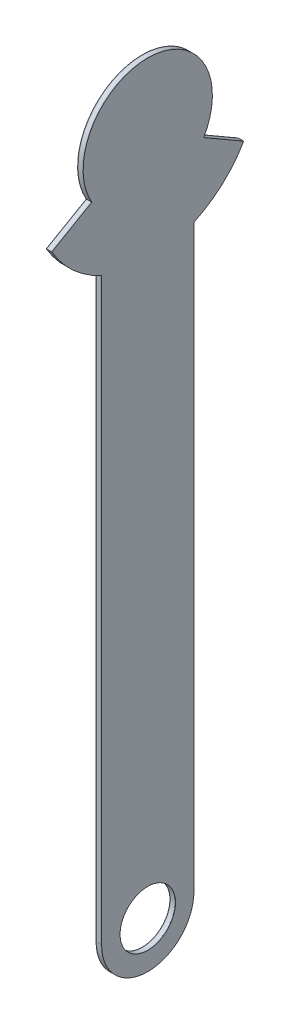
SolidWorks part; units mm, degrees
ref_plane "Front Plane" through (0, 0, 0) normal (0, 0, 1) x (1, 0, 0)
ref_plane "Top Plane" through (0, 0, 0) normal (0, 1, 0) x (1, 0, 0)
ref_plane "Right Plane" through (0, 0, 0) normal (1, 0, 0) x (0, 0, -1)
sketch "Sketch2" plane through (0, 0, 0) normal (1, 0, 0) x (0, 0, -1)
  line L0 (0, -196.8) -> (0, 196.8) construction
  line L2 (-30.3109, 179.3) -> (-51.9615, 166.8)
  line L3 (30.3109, 179.3) -> (51.9615, 166.8)
  line L9 (-25, 142.2564) -> (-25, -171.8)
  line L10 (25, 142.2564) -> (25, -171.8)
  circle A0 centre (0, 196.8) radius 35
  arc A1 (-51.9615, 166.8) -> (51.9615, 166.8) centre (0, 196.8) ccw
  arc A2 (-25, -171.8) -> (25, -171.8) centre (0, -171.8) ccw
  circle A3 centre (0, -171.8) radius 15
  point P4 (0, 0)
  point P15 (0, 196.8)
  dimension "D2" = 70
  dimension "D3" = 120
  dimension "D7" = 50
  dimension "D8" = 30
  dimension "D1" = 393.6
extrude "Boss-Extrude1" add sketch "Sketch2" along normal blind 0.25 contours A0 | A1 L0 A0 L2 | L0 A1 L3 A0 | L0 A2 L10 A1 A3 | A2 L0 A3 A1 L9 region at (0, -19.9643, 12.6927) region at (0, -19.9643, -12.6927) region at (0, 156.611, 23.2031) region at (0, 156.611, -23.2031) region at (0, 167.3464, 17.005)
sketch "Sketch3" plane through (0, 0, 0) normal (-1, 0, 0) x (0, 0, 1)
  circle A3 centre (0, -171.8) radius 15
  circle A4 centre (0, -171.8) radius 15
  circle M10 centre (0, -171.8) radius 15
  arc M11 (30.3109, 179.3) -> (-30.3109, 179.3) centre (0, 196.8) ccw
  line M12 (-30.3109, 179.3) -> (-51.9615, 166.8)
  arc M13 (-51.9615, 166.8) -> (-25, 142.2564) centre (0, 196.8) ccw
  line M14 (-25, 142.2564) -> (-25, -171.8)
  arc M15 (-25, -171.8) -> (25, -171.8) centre (0, -171.8) ccw
  line M16 (25, -171.8) -> (25, 142.2564)
  arc M17 (25, 142.2564) -> (51.9615, 166.8) centre (0, 196.8) ccw
  line M18 (51.9615, 166.8) -> (30.3109, 179.3)
  dimension "D1" = 0
extrude "Boss-Extrude2" add sketch "Sketch3" along normal blind 2.5 separate body contours M18 M11 M12 M13 M14 M15 M16 M17 M10
sketch "Sketch4" plane through (-2.5, 0, 0) normal (-1, 0, 0) x (0, 0, 1)
  circle A1 centre (0, -171.8) radius 15
  circle A2 centre (0, -171.8) radius 15
  line M2 (51.9615, 166.8) -> (30.3109, 179.3)
  arc M3 (30.3109, 179.3) -> (-30.3109, 179.3) centre (0, 196.8) ccw
  line M4 (-30.3109, 179.3) -> (-51.9615, 166.8)
  arc M5 (-51.9615, 166.8) -> (-25, 142.2564) centre (0, 196.8) ccw
  line M6 (-25, 142.2564) -> (-25, -171.8)
  arc M7 (-25, -171.8) -> (25, -171.8) centre (0, -171.8) ccw
  line M8 (25, -171.8) -> (25, 142.2564)
  arc M9 (25, 142.2564) -> (51.9615, 166.8) centre (0, 196.8) ccw
  circle M10 centre (0, -171.8) radius 15
  dimension "D1" = 0
extrude "Boss-Extrude3" add sketch "Sketch4" along normal blind 0.25 separate body contours M9 M2 M3 M4 M5 M6 M7 M8 M10 region at (-2.5, 37.5769, 0)
sketch "Sketch5" plane through (0.25, 0, 0) normal (1, 0, 0) x (0, 0, -1)
  circle A0 centre (0, 196.8) radius 17.5 construction
  circle A1 centre (0, 196.8) radius 12 construction
  point P4 (0, 208.8)
  point P7 (11.4127, 200.5082)
  point P8 (7.0534, 187.0918)
  point P9 (-7.0534, 187.0918)
  point P10 (-11.4127, 200.5082)
  dimension "D1" = 35
  dimension "D2" = 24
  dimension "D3" = 5
